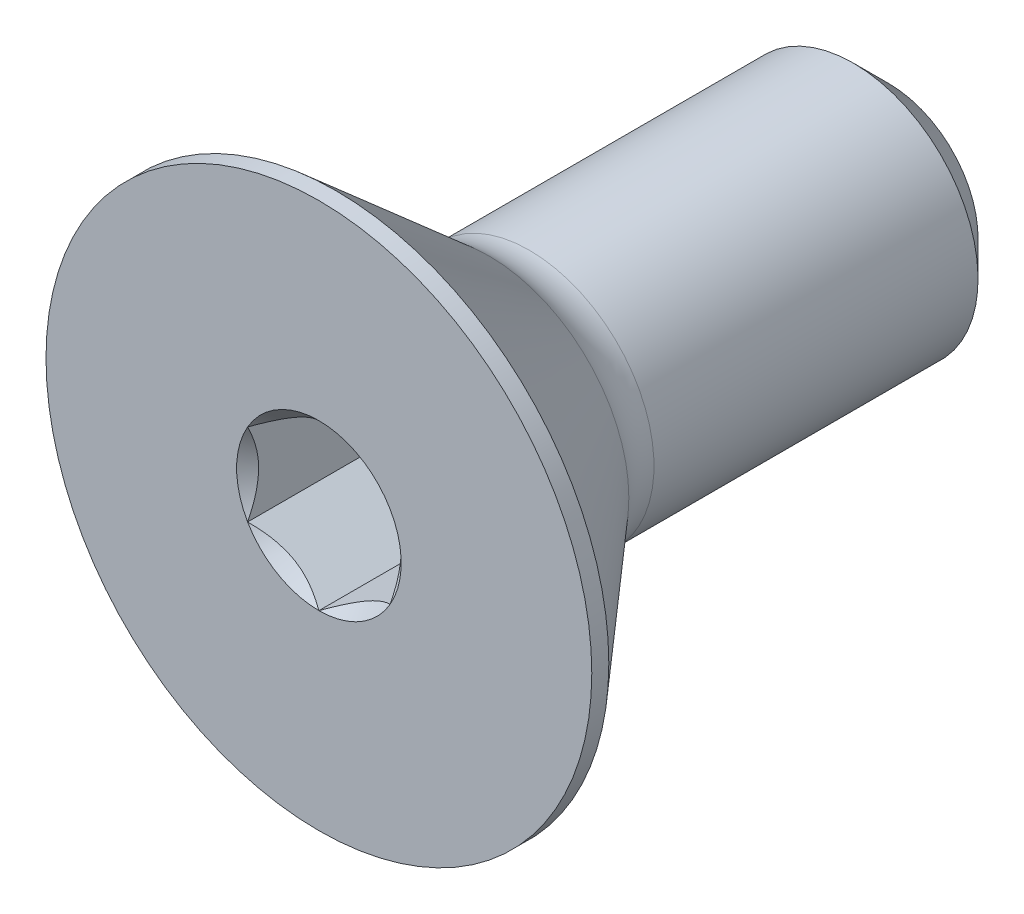
SolidWorks part; units mm, degrees
ref_plane "Front" through (0, 0, 0) normal (0, 0, 1) x (1, 0, 0)
ref_plane "Top" through (0, 0, 0) normal (0, 1, 0) x (1, 0, 0)
ref_plane "Right" through (0, 0, 0) normal (1, 0, 0) x (0, 0, -1)
sketch "Sketch1" plane through (0, 0, 0) normal (1, 0, 0) x (0, 0, -1)
  line L0 (0, 4.5593) -> (0.2845, 4.5593) construction
  line L1 (0.2845, 4.5593) -> (2.8448, 2.3336) construction
  line L2 (0, 2.0828) -> (9.525, 2.0828)
  line L3 (9.525, 2.0828) -> (9.525, 0)
  line L4 (9.525, 0) -> (0, 0)
  line L5 (0, 0) -> (0, 4.5593) construction
  line L6 (0, 4.5593) -> (0, -4.5593) construction
  line L7 (9.525, 2.0828) -> (9.525, -2.0828) construction
  line L8 (0, -4.5593) -> (0.2845, -4.5593) construction
  line L9 (0.2845, -4.5593) -> (2.8448, -2.3336) construction
  line L11 (0, 2.0828) -> (0, 0)
  line L12 (3.5157, 2.0828) -> (3.5157, 0) construction
  arc A1 (2.8448, 2.3336) -> (3.5157, 2.0828) centre (3.5157, 3.1055) ccw construction
  dimension "D1" = 0.2845
  dimension "Head Ht" = 2.8448
  dimension "Head Dia" = 9.1186
  dimension "Dia" = 4.1656
  dimension "Lg" = 9.525
  dimension "Head Angle" = 82
revolve "Revolve1" add sketch "Sketch1" angle 360 mid plane about L4
sketch "Sketch3" plane through (0, 0, -9.525) normal (0, 0, -1) x (-1, 0, 0)
  circle A0 centre (0, 0) radius 2.0828
curve "Helix/Spiral1" pitch 0.7937 height 9.525 turns 12
sketch "Sketch2" plane through (0, 0, 0) normal (1, 0, 0) x (0, 0, -1)
  line L0 (9.525, 2.0828) -> (10.2195, 2.0828)
  line L1 (10.2195, 2.0828) -> (9.9219, 1.5672)
  line L2 (9.9219, 1.5672) -> (9.8227, 1.5672)
  line L3 (9.8227, 1.5672) -> (9.525, 2.0828)
  line L4 (9.6738, 1.825) -> (10.0707, 1.825) construction
  dimension "D1" = 60
  dimension "D2" = 0.0992
  dimension "D3" = 0.3969
chamfer "Chamfer1" distance 0.5953 angle 45 1 edges at (0, 2.0828, -9.525)
sweep "Cut-Sweep1" [suppressed] cut profiles "Sketch2" path "Helix/Spiral1"
sketch "Sketch7" plane through (0, 0, 0) normal (1, 0, 0) x (0, 0, -1)
  line L0 (0, 4.5593) -> (0.2845, 4.5593) construction
  line L1 (0.2845, 4.5593) -> (2.8448, 2.3336) construction
  line L2 (0, 4.5593) -> (0.2845, 4.5593)
  line L3 (0.2845, 4.5593) -> (2.8448, 2.3336)
  line L4 (3.5157, 2.0828) -> (3.5157, 0) construction
  line L5 (3.5157, 2.0828) -> (3.5157, 0)
  line L7 (0, 0) -> (0, 4.5593) construction
  line L8 (0, 0) -> (0, 4.5593)
  line L9 (0, 0) -> (3.5157, 0)
  line L10 (5.0152, 0) -> (-5.0152, 0) construction
  arc A0 (2.8448, 2.3336) -> (3.5157, 2.0828) centre (3.5157, 3.1055) ccw construction
  arc A1 (2.8448, 2.3336) -> (3.5157, 2.0828) centre (3.5157, 3.1055) ccw
revolve "Revolve2" add sketch "Sketch7" angle 360 mid plane about L9
ref_plane "Plane1" through (0, 0, -3.5157) normal (0, 0, 1) x (1, 0, 0)
sketch "Sketch8" plane through (0, 0, -3.5157) normal (0, 0, 1) x (1, 0, 0)
  circle A0 centre (0, 0) radius 2.0828
extrude "Boss-Extrude1" add sketch "Sketch8" against normal through all draft 45
sketch "Sketch5" plane through (0, 0, 0) normal (0, 0, 1) x (1, 0, 0)
  line L1 (1.1906, -0.6874) -> (1.1906, 0.6874)
  line L2 (1.1906, 0.6874) -> (0, 1.3748)
  line L3 (0, 1.3748) -> (-1.1906, 0.6874)
  line L4 (-1.1906, 0.6874) -> (-1.1906, -0.6874)
  line L5 (-1.1906, -0.6874) -> (0, -1.3748)
  line L6 (0, -1.3748) -> (1.1906, -0.6874)
  circle A0 centre (0, 0) radius 1.1906 construction
  dimension "Hex" = 2.3813
extrude "Cut-Extrude2" cut sketch "Sketch5" against normal blind 1.9914
sketch "Sketch6" plane through (0, 0, 0) normal (0, 0, 1) x (1, 0, 0)
  circle A0 centre (0, 0) radius 1.3748
extrude "Cut-Extrude3" cut sketch "Sketch6" against normal blind 1.9914 draft 45
sketch "Sketch9" [suppressed] plane through (0, 0, -3.5157) normal (0, 0, 1) x (1, 0, 0)
  circle A1 centre (0, 0) radius 2.0828
  circle A2 centre (0, 0) radius 2.0828
  point P0 (0, 2.0828)
  dimension "D1" = 0
extrude "Boss-Extrude2" [suppressed] add sketch "Sketch9" against normal offset from surface (6.0093 mm away) 22.225
sketch "Sketch10" plane through (0, 0, 0) normal (1, 0, 0) x (0, 0, -1)
  line L0 (9.525, 2.0828) -> (9.525, -2.0828) construction
  point P0 (8.3344, -2.0828)
  dimension "D1" = 1.1906
equation "\"D3@Helix/Spiral1\" = \"Lg@Sketch1\""
equation "\"D2@Sketch2\" = \"D4@Helix/Spiral1\" * .125"
equation "\"D3@Sketch2\" = \"D4@Helix/Spiral1\" * .5"
equation "\"D1@Chamfer1\" = \"D4@Helix/Spiral1\" * .75"
equation "\"D1@Cut-Extrude2\" = \"Head Ht@Sketch1\" * .7"
equation "\"D1@Sketch1\" = \"Head Ht@Sketch1\" * .1"
equation "\"D1@Sketch10\" = \"D4@Helix/Spiral1\" * 1.5"
equation "\"D1@Cut-Extrude3\" = \"D1@Cut-Extrude2\""
